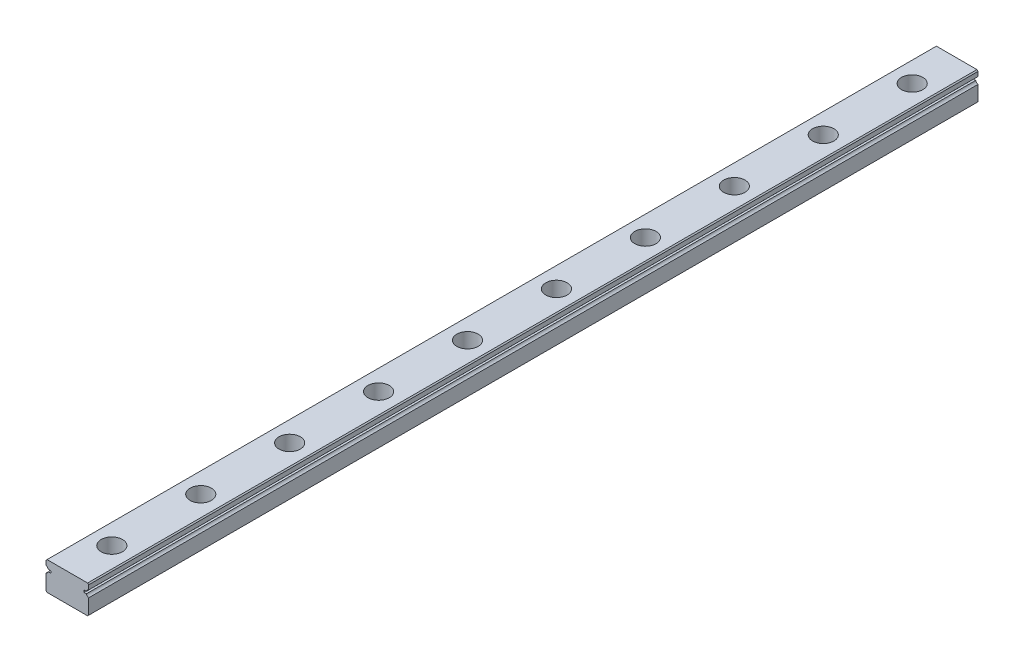
SolidWorks part; units mm, degrees
ref_plane "Спереди" through (0, 0, 0) normal (0, 0, 1) x (1, 0, 0)
ref_plane "Сверху" through (0, 0, 0) normal (0, 1, 0) x (1, 0, 0)
ref_plane "Справа" through (0, 0, 0) normal (1, 0, 0) x (0, 0, -1)
sketch "Эскиз1" plane through (0, 0, 0) normal (0, 0, 1) x (1, 0, 0)
  line L0 (-6, 3.7) -> (-5.7, 4)
  line L1 (-5.7, -4) -> (5.7, -4)
  line L2 (-6, -3.7) -> (-6, 0.549)
  line L3 (-5.7, 4) -> (5.7, 4)
  line L4 (6, -3.7) -> (6, 0.549)
  line L5 (-6, -4) -> (6, 4) construction
  line L6 (-6, 4) -> (6, -4) construction
  line L7 (-6, -3.7) -> (-5.7, -4)
  line L8 (5.7, -4) -> (6, -3.7)
  line L9 (5.7, 4) -> (6, 3.7)
  line L10 (-6, 2.451) -> (-6, 3.7)
  line L11 (-5.3546, 1.7981) -> (-4.6435, 1.7981)
  line L12 (0, 5.4188) -> (0, -5.747) construction
  line L13 (-5.3546, 1.2019) -> (-4.6435, 1.2019)
  line L14 (-4.6435, 1.7981) -> (-4.6435, 1.2019)
  line L15 (4.6435, 1.7981) -> (4.6435, 1.2019)
  line L16 (5.3546, 1.2019) -> (4.6435, 1.2019)
  line L17 (5.3546, 1.7981) -> (4.6435, 1.7981)
  line L18 (6, 2.451) -> (6, 3.7)
  line L19 (4.6435, 1.7981) -> (5.3546, 1.7981) construction
  arc A0 (-6, 0.549) -> (-5.3546, 1.2019) centre (-6.3091, 1.5) ccw
  arc A1 (-5.3546, 1.7981) -> (-6, 2.451) centre (-6.3091, 1.5) ccw
  arc A2 (5.3546, 1.7981) -> (6, 2.451) centre (6.3091, 1.5) cw
  arc A3 (6, 0.549) -> (5.3546, 1.2019) centre (6.3091, 1.5) cw
  point P0 (0, 0)
extrude "Бобышка-Вытянуть1" add sketch "Эскиз1" along normal blind 250
sketch "Эскиз2" plane through (0, 4, 0) normal (0, 1, 0) x (1, 0, 0)
  line L0 (0, 0) -> (0, -26.2396) construction
  line L1 (5.7, 0) -> (-5.7, 0) construction
  line L2 (-3.8306, -12.5) -> (3.8306, -12.5) construction
  circle A0 centre (0, -12.5) radius 3
  circle A1 centre (0, -12.5) radius 1.75
  dimension "D2" = 3.5
  dimension "D3" = 6
  dimension "D1" = 12.5
extrude "Вырез-Вытянуть1" cut sketch "Эскиз2" against normal blind 4.5
extrude "Вырез-Вытянуть2" cut sketch "Эскиз2<2>" against normal through all contours A1 region at (0, 4, 12.5)
sketch "Эскиз2<2>" plane through (0, 4, 0) normal (0, 1, 0) x (1, 0, 0) same geometry as "Эскиз2"
pattern_linear "Линейный массив1" count 10 spacing 25 along (0, 0, 1) of "Вырез-Вытянуть1", "Вырез-Вытянуть2"
